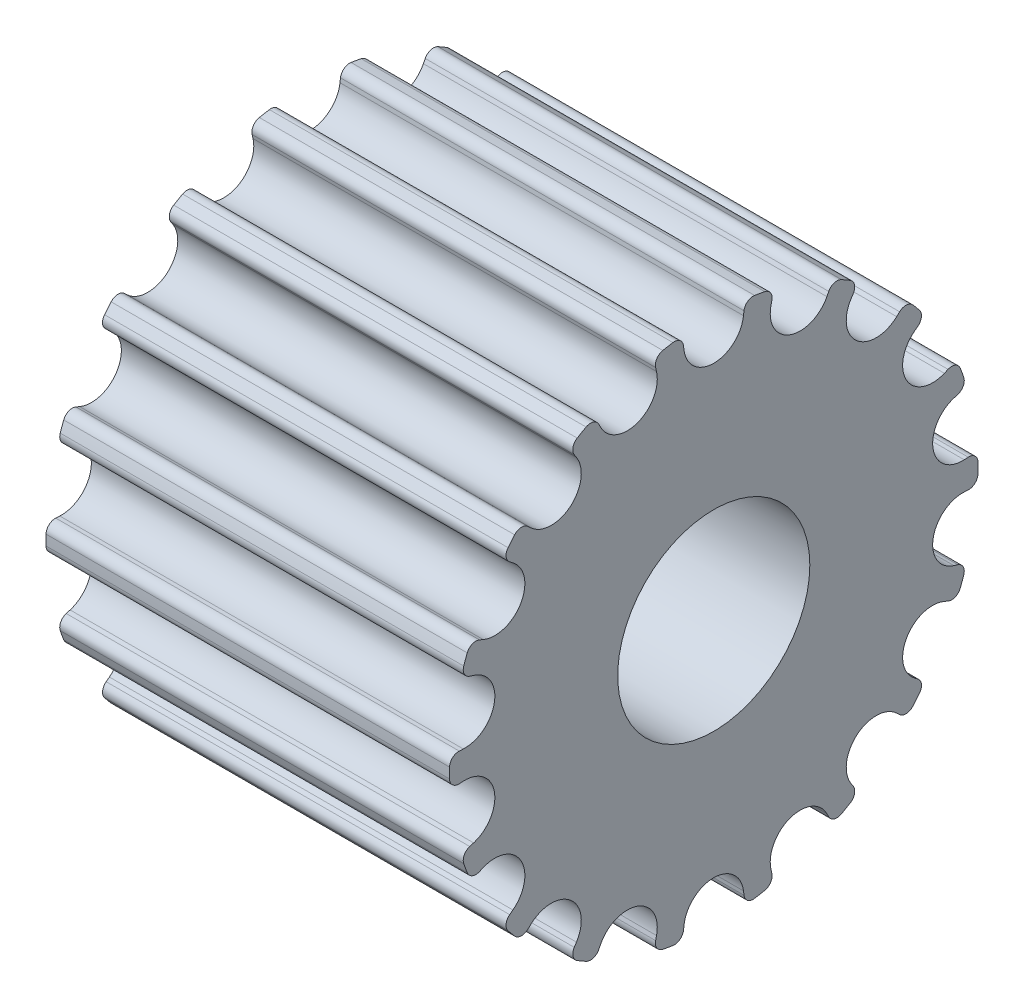
SolidWorks part; units mm, degrees
ref_plane "前视基准面" through (0, 0, 0) normal (0, 0, 1) x (1, 0, 0)
ref_plane "上视基准面" through (0, 0, 0) normal (0, 1, 0) x (1, 0, 0)
ref_plane "右视基准面" through (0, 0, 0) normal (1, 0, 0) x (0, 0, -1)
sketch "草图1" plane through (0, 0, 0) normal (0, 0, 1) x (1, 0, 0)
  line L0 (0, 0) -> (64.8368, 0) construction
  line L1 (0, 2.7506) -> (0, 13.753)
  line L2 (0, 13.753) -> (28, 13.753)
  line L3 (28, 13.753) -> (28, 5.5012)
  line L4 (28, 5.5012) -> (20, 5.5012)
  line L5 (20, 5.5012) -> (20, 2.7506)
  line L6 (20, 2.7506) -> (0, 2.7506)
  dimension "L" = 20
  dimension "B" = 28
  dimension "d" = 5.5012
  dimension "d1" = 11.0024
  dimension "da" = 27.506
revolve "旋转1" add sketch "草图1" angle 360 about L0
chamfer "倒角1" distance 1 angle 45 2 edges at (20, 0, 2.7506) (0, 0, 2.7506)
sketch "草图4" plane through (0, 0, 0) normal (-1, 0, 0) x (0, 0, 1)
  line L1 (-1, 2.5624) -> (1, 2.5624)
  line L2 (-1, 2.5624) -> (-1, 3.5624)
  line L3 (-1, 3.5624) -> (1, 3.5624)
  line L4 (1, 2.5624) -> (1, 3.5624)
  circle A0 centre (0, 0) radius 2.7506 construction
  dimension "键槽宽度" = 2
  dimension "t1" = 1
extrude "切除-拉伸1" cut sketch "草图4" against normal through all
ref_axis "基准轴1" through (-1.4, 0, 0) along (1, 0, 0)
sketch "草图6" plane through (0, 0, 0) normal (1, 0, 0) x (0, 0, -1)
  line L0 (0, 0) -> (0, 30.6512) construction
  line L1 (1.5741, 13.1722) -> (1.5484, 12.9629)
  line L2 (2.5975, 13.5055) -> (2.7942, 15.107)
  line L3 (-2.5975, 13.5055) -> (-2.7942, 15.107)
  line L4 (-1.5741, 13.1722) -> (-1.5484, 12.9629)
  circle A0 centre (0, 0) radius 13.753 construction
  circle A1 centre (0, 0) radius 11.593 construction
  arc A2 (-1.5484, 12.9629) -> (1.5484, 12.9629) centre (0, 13.153) ccw
  arc A3 (2.7942, 15.107) -> (-2.7942, 15.107) centre (0, 0) ccw
  arc A4 (1.5741, 13.1722) -> (2.1246, 13.5879) centre (2.0505, 13.1137) cw
  arc A5 (2.1246, 13.5879) -> (2.5975, 13.5055) centre (0, 0) cw
  arc A6 (-2.1246, 13.5879) -> (-2.5975, 13.5055) centre (0, 0) ccw
  arc A7 (-1.5741, 13.1722) -> (-2.1246, 13.5879) centre (-2.0505, 13.1137) ccw
  point P7 (0, 3.25)
  point P8 (0, 28.4912)
  point P15 (1.6334, 13.6557)
  dimension "D1" = 23.186
  dimension "ra" = 0.48
  dimension "rf" = 1.56
  dimension "hg" = 2.16
  dimension "D3" = 0.48
  dimension "D4" = 1.6136
  dimension "angle" = 14
  dimension "bw" = 3.25
extrude "切除-拉伸2" cut sketch "草图6" along normal up to next
pattern_circular "阵列(圆周)3" count 18 over 360 about axis through (-1.4, 0, 0) along (1, 0, 0) of "切除-拉伸2"
sketch "草图7" plane through (28, 0, 0) normal (1, 0, 0) x (0, 0, -1)
  circle A0 centre (0, 0) radius 16.5709
  dimension "D1" = 33.1417
extrude "切除-拉伸3" cut sketch "草图7" against normal blind 7
sketch "草图8" plane through (21, 0, 0) normal (1, 0, 0) x (0, 0, -1)
  circle A0 centre (0, 0) radius 8.7924
  dimension "D1" = 17.5848
extrude "凸台-拉伸1" add sketch "草图8" against normal up to surface (21 mm away) up to face at (0, 0, -3.7506)
sketch "草图9" plane through (21, 0, 0) normal (1, 0, 0) x (0, 0, -1)
  circle A0 centre (0, 0) radius 5
  dimension "D1" = 10
extrude "切除-拉伸4" cut sketch "草图9" against normal up to surface (21 mm away) up to face at (0, 0, 0)
equation "\"D1@草图6\" = \"da@草图1\"  - \"hg@草图6\" - \"hg@草图6\""
equation "\"D3@草图6\" = \"ra@草图6\""
